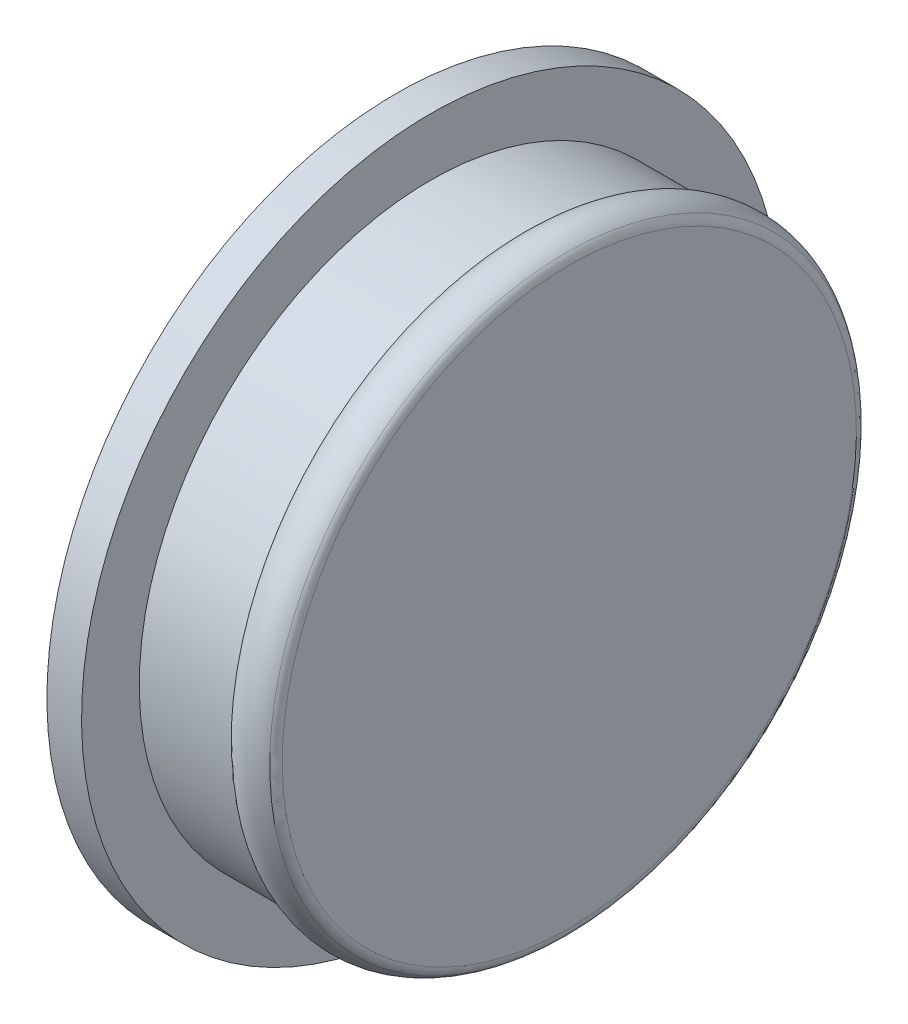
SolidWorks part; units mm, degrees
material "Plain Carbon Steel"
ref_plane "Front Plane" through (0, 0, 0) normal (0, 0, 1) x (1, 0, 0)
ref_plane "Top Plane" through (0, 0, 0) normal (0, 1, 0) x (1, 0, 0)
ref_plane "Right Plane" through (0, 0, 0) normal (1, 0, 0) x (0, 0, -1)
sketch "Sketch1" plane through (0, 0, 0) normal (0, 0, 1) x (1, 0, 0)
  line L1 (-0.508, 7.6835) -> (-0.508, 6.4135)
  line L2 (-0.508, 6.4135) -> (1.524, 6.4135)
  line L3 (2.54, 6.4135) -> (2.54, 0)
  line L4 (2.54, 0) -> (1.27, 0)
  line L5 (1.27, 0) -> (1.27, 5.1435)
  line L6 (1.27, 5.1435) -> (-1.27, 5.1435)
  line L7 (-1.27, 5.1435) -> (-1.27, 7.6835)
  line L10 (-1.27, 7.6835) -> (-0.508, 7.6835)
  line L11 (2.54, 0) -> (1.4662, 0.2493) construction
  line L12 (-6.5033, 0) -> (2.54, 0) construction
  arc A0 (2.54, 6.4135) -> (1.524, 6.4135) centre (2.032, 6.0325) ccw
  point P11 (0, 5.1435)
  point P14 (1.524, 6.35)
  point P15 (0, 0)
  dimension "D9" = 0.254
  dimension "D1" = 12.827
  dimension "D2" = 3.81
  dimension "D3" = 1.27
  dimension "D4" = 0.762
  dimension "D5" = 1.27
  dimension "D6" = 1.27
  dimension "D7" = 1.016
  dimension "D8" = 2.032
revolve "Revolve1" add sketch "Sketch1" angle 360 about L12
chamfer "Chamfer1" distance 1.27 angle 50 1 edges at (1.27, -5.1435, 0) first distance on face at (1.27, -5.1435, 0)
fillet "Fillet1" radius 0.254 1 edges at (2.54, -6.4135, 0)
chamfer "Chamfer3" distance 1.27 angle 45 1 edges at (-1.27, -5.1435, 0)
fillet "Fillet2" radius 0.254 1 edges at (0, 5.1435, 0)
